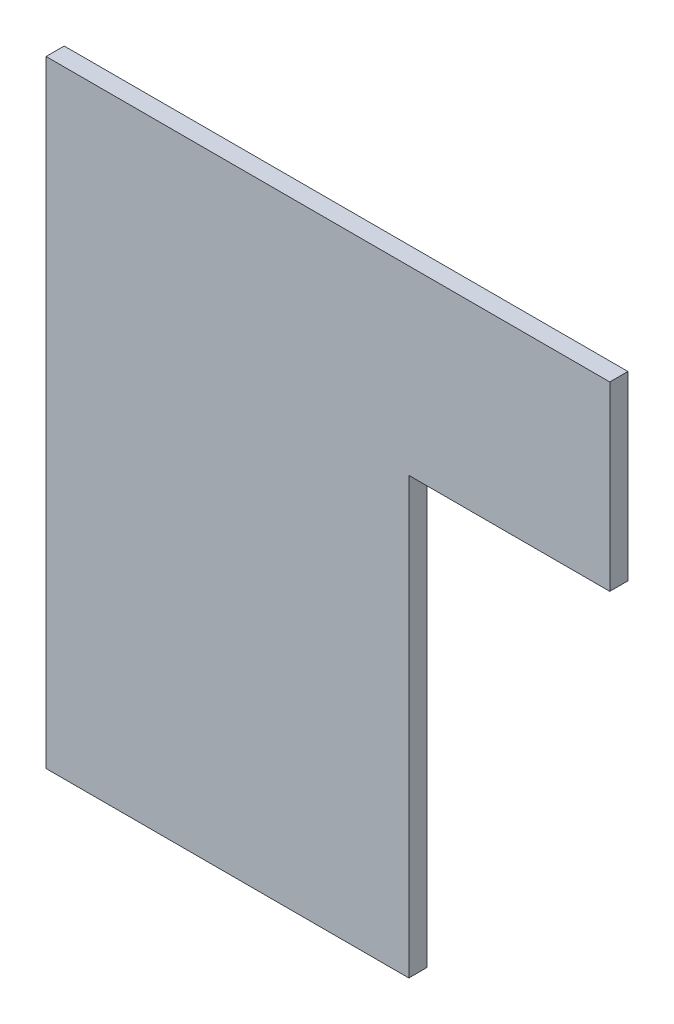
SolidWorks part; units mm, degrees
ref_plane "Front Plane" through (0, 0, 0) normal (0, 0, 1) x (1, 0, 0)
ref_plane "Top Plane" through (0, 0, 0) normal (0, 1, 0) x (1, 0, 0)
ref_plane "Right Plane" through (0, 0, 0) normal (1, 0, 0) x (0, 0, -1)
sketch "Sketch1" plane through (0, 0, 0) normal (0, 0, 1) x (1, 0, 0)
  line L1 (0, 0) -> (63.5, 0)
  line L2 (0, 0) -> (0, 107.95)
  line L3 (0, 107.95) -> (63.5, 107.95)
  line L4 (63.5, 0) -> (63.5, 76.2)
  line L5 (63.5, 107.95) -> (98.679, 107.95)
  line L7 (63.5, 76.2) -> (98.679, 76.2)
  line L8 (98.679, 107.95) -> (98.679, 76.2)
  point P8 (0, 0)
  point P9 (0, 0)
  dimension "D1" = 107.95
  dimension "D2" = 63.5
  dimension "D3" = 35.179
  dimension "D4" = 76.2
extrude "Boss-Extrude1" add sketch "Sketch1" along normal blind 3.175
